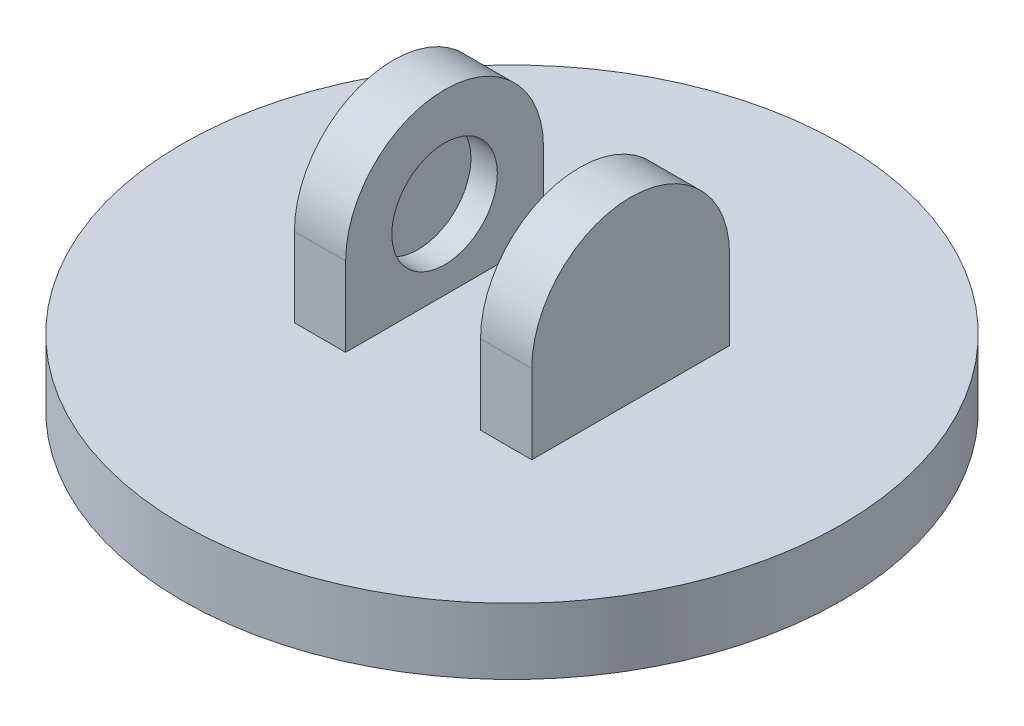
SolidWorks part; units mm, degrees
ref_plane "Front Plane" through (0, 0, 0) normal (0, 0, 1) x (1, 0, 0)
ref_plane "Top Plane" through (0, 0, 0) normal (0, 1, 0) x (1, 0, 0)
ref_plane "Right Plane" through (0, 0, 0) normal (1, 0, 0) x (0, 0, -1)
sketch "Sketch1" plane through (0, 0, 0) normal (0, 1, 0) x (1, 0, 0)
  circle A0 centre (0, 0) radius 150
extrude "Boss-Extrude1" add sketch "Sketch1" along normal blind 50
sketch "Sketch2" plane through (0, 50, 0) normal (0, 1, 0) x (1, 0, 0)
  line L1 (90, -75) -> (-90, -75)
  line L2 (90, -75) -> (90, 75)
  line L3 (90, 75) -> (-90, 75)
  line L4 (-90, -75) -> (-90, 75)
  line L5 (90, -75) -> (-90, 75) construction
  line L6 (90, 75) -> (-90, -75) construction
  point P0 (0, 0)
  dimension "D1" = 150
  dimension "D2" = 180
extrude "Boss-Extrude2" add sketch "Sketch2" along normal blind 120
sketch "Sketch3" plane through (90, 0, 0) normal (1, 0, 0) x (0, 0, -1)
  line L0 (-75, 110) -> (-75, 50)
  line L1 (-75, 170) -> (-75, 50) construction
  line L2 (75, 170) -> (75, 50) construction
  line L4 (-75, 50) -> (75, 50)
  line L5 (75, 50) -> (75, 110)
  arc A0 (-75, 110) -> (75, 110) centre (0, 110) cw
sketch "Sketch4" plane through (-90, 0, 0) normal (-1, 0, 0) x (0, 0, 1)
  line L0 (75, 110) -> (-75, 110)
  line L1 (-75, 110) -> (-75, 170)
  line L2 (-75, 170) -> (75, 170)
  line L3 (75, 170) -> (75, 110)
extrude "Cut-Extrude1" cut sketch "Sketch4" against normal blind 180
extrude "Boss-Extrude3" add sketch "Sketch3" against normal blind 180 contours A0 L5 L4 L0
sketch "Sketch5" plane through (0, 0, 75) normal (0, 0, 1) x (1, 0, 0)
  line L0 (0, 110) -> (0, 185)
  line L1 (90, 110) -> (-90, 110) construction
  line L2 (90, 185) -> (-90, 185) construction
  line L4 (51.1336, 110) -> (-51.1336, 110)
  line L5 (51.1336, 110) -> (51.1336, 185)
  line L6 (51.1336, 185) -> (-51.1336, 185)
  line L7 (-51.1336, 110) -> (-51.1336, 185)
  line L8 (51.1336, 110) -> (-51.1336, 185) construction
  line L9 (51.1336, 185) -> (-51.1336, 110) construction
  point P6 (0, 147.5)
  dimension "D1" = 102.2672
extrude "Cut-Extrude3" cut sketch "Sketch5" against normal blind 180 contours L6 L7 L4 L5
sketch "Sketch8" plane through (-51.1336, 0, 0) normal (1, 0, 0) x (0, 0, -1)
  line L0 (75, 110) -> (-75, 110) construction
  line L1 (-75, 110) -> (75, 110)
  arc A0 (75, 110) -> (-75, 110) centre (0, 110) cw
  arc A1 (75, 110) -> (-75, 110) centre (0, 110) ccw construction
extrude "Cut-Extrude4" cut sketch "Sketch8" along normal blind 100
sketch "Sketch10" plane through (48.8664, 0, 0) normal (-1, 0, 0) x (0, 0, 1)
  line L0 (-75, 110) -> (75, 110) construction
  line L1 (-75, 110) -> (75, 110)
  arc A0 (-75, 110) -> (75, 110) centre (0, 110) ccw
extrude "Cut-Extrude5" cut sketch "Sketch10" against normal blind 2.2672
sketch "Sketch11" plane through (-51.1336, 0, 0) normal (1, 0, 0) x (0, 0, -1)
  circle A0 centre (0, 110) radius 40
  circle A1 centre (0, 110) radius 40
sketch "Sketch12" plane through (51.1336, 0, 0) normal (-1, 0, 0) x (0, 0, 1)
  circle A0 centre (0, 110) radius 40
extrude "Cut-Extrude6" cut sketch "Sketch12" against normal blind 20
extrude "Cut-Extrude7" cut sketch "Sketch11" against normal blind 20 contours A0
sketch "Sketch15" plane through (0, 0, 75) normal (0, 0, 1) x (1, 0, 0)
  line L0 (-90, 50) -> (90, 50) construction
  line L1 (-51.1336, 110) -> (51.1336, 110)
  line L2 (-51.1336, 110) -> (-51.1336, 50)
  line L3 (-51.1336, 50) -> (51.1336, 50)
  line L4 (51.1336, 110) -> (51.1336, 50)
extrude "Cut-Extrude8" cut sketch "Sketch15" against normal blind 408
sketch "Sketch16" plane through (0, 0, 0) normal (0, -1, 0) x (1, 0, 0)
  circle A0 centre (0, 0) radius 250
extrude "Boss-Extrude4" add sketch "Sketch16" against normal blind 50 contours A0
